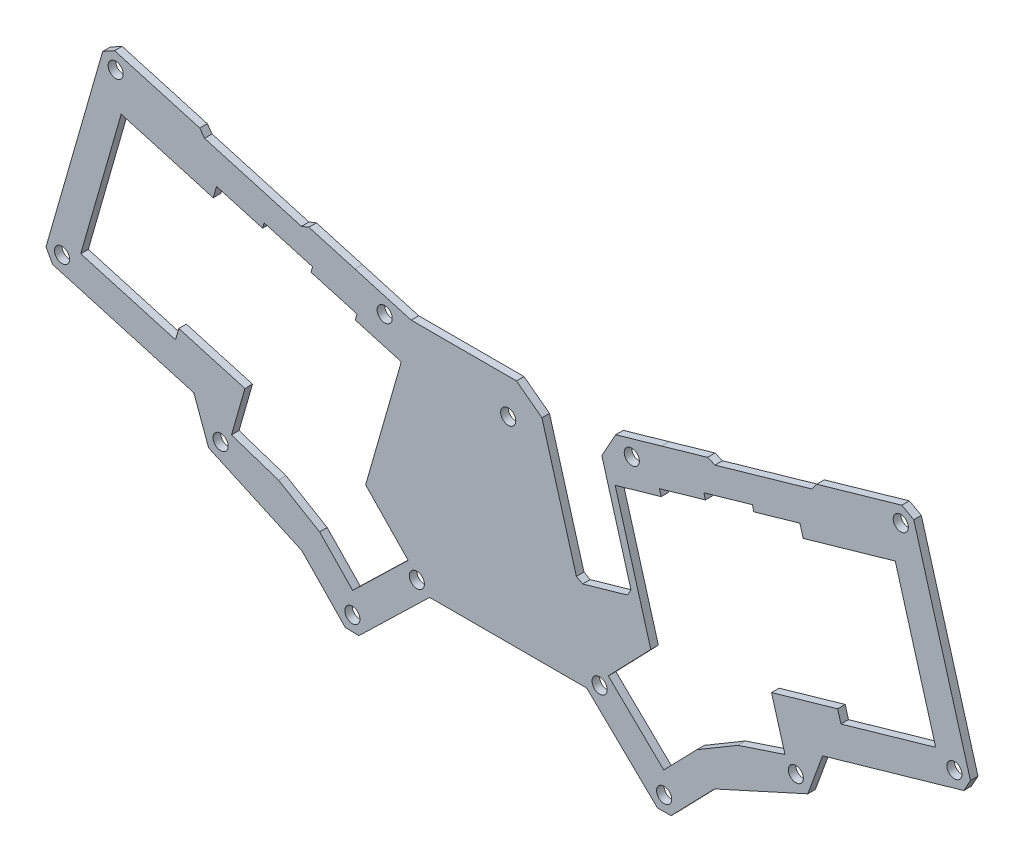
SolidWorks part; units mm, degrees
ref_plane "Plan de face" through (0, 0, 0) normal (0, 0, 1) x (1, 0, 0)
ref_plane "Plan de dessus" through (0, 0, 0) normal (0, 1, 0) x (1, 0, 0)
ref_plane "Plan de droite" through (0, 0, 0) normal (1, 0, 0) x (0, 0, -1)
sketch "Esquisse1" plane through (0, 0, 0) normal (0, 0, 1) x (1, 0, 0)
  line L0 (-121.6461, -32.0475) -> (-108.1875, -28.1884) construction
  line L1 (-108.1875, -28.1884) -> (-104.3283, -41.647) construction
  line L2 (-104.3283, -41.647) -> (-117.7869, -45.5062) construction
  line L3 (-117.7869, -45.5062) -> (-121.6461, -32.0475) construction
  line L4 (-100.1763, -37.9855) -> (-104.0355, -24.5269) construction
  line L5 (-104.0355, -24.5269) -> (-90.5769, -20.6677) construction
  line L6 (-90.5769, -20.6677) -> (-86.7177, -34.1263) construction
  line L7 (-86.7177, -34.1263) -> (-100.1763, -37.9855) construction
  line L8 (-82.5657, -30.4649) -> (-86.4249, -17.0063) construction
  line L9 (-86.4249, -17.0063) -> (-72.9663, -13.1471) construction
  line L10 (-72.9663, -13.1471) -> (-69.1071, -26.6057) construction
  line L11 (-69.1071, -26.6057) -> (-82.5657, -30.4649) construction
  line L12 (-63.6458, -27.5106) -> (-67.505, -14.0519) construction
  line L13 (-67.505, -14.0519) -> (-54.0463, -10.1927) construction
  line L14 (-54.0463, -10.1927) -> (-50.1872, -23.6514) construction
  line L15 (-50.1872, -23.6514) -> (-63.6458, -27.5106) construction
  line L16 (-44.0711, -26.8394) -> (-47.9303, -13.3808) construction
  line L17 (-47.9303, -13.3808) -> (-34.4717, -9.5216) construction
  line L18 (-34.4717, -9.5216) -> (-30.6125, -22.9802) construction
  line L19 (-30.6125, -22.9802) -> (-44.0711, -26.8394) construction
  line L20 (-25.8054, -21.6018) -> (-29.6646, -8.1432) construction
  line L21 (-29.6646, -8.1432) -> (-16.206, -4.284) construction
  line L22 (-16.206, -4.284) -> (-12.3468, -17.7426) construction
  line L23 (-12.3468, -17.7426) -> (-25.8054, -21.6018) construction
  line L24 (-116.4086, -50.3128) -> (-102.95, -46.4536) construction
  line L25 (-102.95, -46.4536) -> (-99.0908, -59.9122) construction
  line L26 (-99.0908, -59.9122) -> (-112.5494, -63.7714) construction
  line L27 (-112.5494, -63.7714) -> (-116.4086, -50.3128) construction
  line L28 (-98.798, -42.7922) -> (-85.3394, -38.933) construction
  line L29 (-85.3394, -38.933) -> (-81.4802, -52.3916) construction
  line L30 (-81.4802, -52.3916) -> (-94.9388, -56.2508) construction
  line L31 (-94.9388, -56.2508) -> (-98.798, -42.7922) construction
  line L32 (-81.1874, -35.2715) -> (-67.7288, -31.4123) construction
  line L33 (-67.7288, -31.4123) -> (-63.8696, -44.8709) construction
  line L34 (-63.8696, -44.8709) -> (-77.3282, -48.7301) construction
  line L35 (-77.3282, -48.7301) -> (-81.1874, -35.2715) construction
  line L36 (-62.2675, -32.3172) -> (-48.8089, -28.458) construction
  line L37 (-48.8089, -28.458) -> (-44.9497, -41.9166) construction
  line L38 (-44.9497, -41.9166) -> (-58.4083, -45.7758) construction
  line L39 (-58.4083, -45.7758) -> (-62.2675, -32.3172) construction
  line L40 (-42.6928, -31.646) -> (-29.2342, -27.7869) construction
  line L41 (-29.2342, -27.7869) -> (-25.375, -41.2455) construction
  line L42 (-25.375, -41.2455) -> (-38.8336, -45.1047) construction
  line L43 (-38.8336, -45.1047) -> (-42.6928, -31.646) construction
  line L44 (-24.4271, -26.4084) -> (-10.9685, -22.5492) construction
  line L45 (-10.9685, -22.5492) -> (-7.1093, -36.0078) construction
  line L46 (-7.1093, -36.0078) -> (-20.5679, -39.867) construction
  line L47 (-20.5679, -39.867) -> (-24.4271, -26.4084) construction
  line L48 (-19.1896, -44.6737) -> (-5.731, -40.8145) construction
  line L49 (-5.731, -40.8145) -> (-1.8718, -54.2731) construction
  line L50 (-1.8718, -54.2731) -> (-15.3304, -58.1323) construction
  line L51 (-15.3304, -58.1323) -> (-19.1896, -44.6737) construction
  line L52 (-37.4554, -49.9113) -> (-23.9967, -46.0521) construction
  line L53 (-23.9967, -46.0521) -> (-20.1376, -59.5107) construction
  line L54 (-20.1376, -59.5107) -> (-33.5962, -63.3699) construction
  line L55 (-33.5962, -63.3699) -> (-37.4554, -49.9113) construction
  line L56 (-57.03, -50.5825) -> (-43.5714, -46.7233) construction
  line L57 (-43.5714, -46.7233) -> (-39.7122, -60.1819) construction
  line L58 (-39.7122, -60.1819) -> (-53.1708, -64.0411) construction
  line L59 (-53.1708, -64.0411) -> (-57.03, -50.5825) construction
  line L60 (-75.9499, -53.5368) -> (-62.4913, -49.6776) construction
  line L61 (-62.4913, -49.6776) -> (-58.6321, -63.1362) construction
  line L62 (-58.6321, -63.1362) -> (-72.0908, -66.9954) construction
  line L63 (-72.0908, -66.9954) -> (-75.9499, -53.5368) construction
  line L64 (-93.5605, -61.0574) -> (-80.1019, -57.1982) construction
  line L65 (-80.1019, -57.1982) -> (-76.2427, -70.6569) construction
  line L66 (-76.2427, -70.6569) -> (-89.7013, -74.516) construction
  line L67 (-89.7013, -74.516) -> (-93.5605, -61.0574) construction
  line L68 (-111.1711, -68.5781) -> (-97.7125, -64.7189) construction
  line L69 (-97.7125, -64.7189) -> (-93.8533, -78.1775) construction
  line L70 (-93.8533, -78.1775) -> (-107.3119, -82.0367) construction
  line L71 (-107.3119, -82.0367) -> (-111.1711, -68.5781) construction
  line L72 (-79.0181, -77.3048) -> (-65.5595, -73.4456) construction
  line L73 (-65.5595, -73.4456) -> (-61.7003, -86.9042) construction
  line L74 (-61.7003, -86.9042) -> (-75.1589, -90.7634) construction
  line L75 (-75.1589, -90.7634) -> (-79.0181, -77.3048) construction
  line L76 (-99.4001, -88.1351) -> (-87.3916, -80.9362)
  line L77 (-87.3916, -80.9362) -> (-80.1927, -92.9448)
  line L78 (-80.1927, -92.9448) -> (-92.2012, -100.1436)
  line L79 (-92.2012, -100.1436) -> (-99.4001, -88.1351)
  line L80 (-120.0498, -100.4367) -> (-110.317, -90.3719)
  line L81 (-110.317, -90.3719) -> (-100.2522, -100.1047)
  line L82 (-100.2522, -100.1047) -> (-109.985, -110.1695)
  line L83 (-109.985, -110.1695) -> (-120.0498, -100.4367)
  line L86 (0.634, -55.7756) -> (-52.9527, -71.1413) construction
  line L89 (-59.2205, -88.2424) -> (-52.9527, -71.1413) construction
  line L96 (-93.4066, -103.0586) -> (-59.4637, -88.3612) construction
  line L97 (-105.418, -115.2057) -> (-93.9754, -103.3509) construction
  line L98 (-126.5332, -96.9919) -> (-107.5003, -115.385) construction
  line L99 (-167.7972, -50.1766) -> (-183.2082, -64.014) construction
  line L100 (-106.3822, -25.4572) -> (-123.6848, -30.4187) construction
  line L101 (-72.1178, -10.6906) -> (-88.4663, -15.3784) construction
  line L102 (-53.2337, -7.6163) -> (-70.5393, -12.5786) construction
  line L103 (-33.6604, -6.9452) -> (-50.9661, -11.9075) construction
  line L104 (-15.3965, -1.7081) -> (-31.745, -6.396) construction
  line L105 (0.5403, -55.2132) -> (-14.6896, -2.0999) construction
  line L106 (-16.199, -60.6113) -> (0.1495, -55.9235) construction
  line L107 (-52.7198, -71.0835) -> (-18.1144, -61.1606) construction
  line L108 (-59.1184, -88.0534) -> (-52.9674, -71.2752) construction
  line L109 (-183.2082, -64.014) -> (-173.1824, -64.9357) construction
  line L113 (-102.2678, -134.438) -> (-84.7238, -116.3191) construction
  line L114 (-84.7238, -116.3191) -> (-47.2969, -99.2981) construction
  line L115 (-47.2969, -99.2981) -> (-41.4917, -83.4594) construction
  line L116 (14.3812, -67.4381) -> (-41.4917, -83.4594) construction
  line L117 (17.8093, -61.2536) -> (-5.1371, 18.7701) construction
  line L122 (-11.3217, 22.1985) -> (-107.4545, -5.3614) construction
  line L129 (-167.7953, -27.6055) -> (-167.7953, -64.7189) construction
  line L130 (-242.0685, -103.8419) -> (-276.37, -88.2424) construction
  line L131 (-229.5108, -116.8112) -> (-242.0685, -103.8419) construction
  line L138 (-208.9328, -96.8551) -> (-229.5108, -116.8112) construction
  line L139 (-225.5107, -79.6567) -> (-208.9328, -96.8551) construction
  line L140 (-109.3352, -134.5492) -> (-102.2678, -134.438) construction
  line L142 (-5.1371, 18.7701) -> (-11.3217, 22.1985) construction
  line L143 (-211.4691, -30.6868) -> (-225.5107, -79.6567) construction
  line L147 (-114.18, -7.2899) -> (-107.4545, -5.3614) construction
  line L148 (-114.18, -7.2899) -> (-123.7936, -10.0465) construction
  line L154 (-118.7579, -16.9241) -> (-12.0005, 13.6817) construction
  line L155 (-131.531, -101.8802) -> (-105.9239, -126.7133) construction
  line L156 (-105.9239, -126.7133) -> (-89.4162, -109.6646) construction
  line L157 (-128.0696, -96.8789) -> (-106.0575, -118.2258)
  line L158 (-106.0575, -118.2258) -> (-92.9354, -104.6737)
  line L161 (1.8709, -56.4612) -> (-35.7408, -67.2462)
  line L162 (1.8709, -56.4612) -> (-14.1861, -0.4639)
  line L163 (-14.1861, -0.4639) -> (-50.7166, -10.9388)
  line L164 (-50.7166, -10.9388) -> (-52.026, -6.3725)
  line L165 (-52.026, -6.3725) -> (-70.2913, -11.61)
  line L166 (-70.2913, -11.61) -> (-70.911, -9.4488)
  line L167 (-70.911, -9.4488) -> (-90.1377, -14.9608)
  line L168 (-90.1377, -14.9608) -> (-89.5177, -17.1231)
  line L169 (-89.5177, -17.1231) -> (-107.783, -22.3606)
  line L170 (-107.783, -22.3606) -> (-107.0938, -24.7639)
  line L171 (-107.0938, -24.7639) -> (-125.3583, -30.0011)
  line L172 (-125.3583, -30.0011) -> (-111.2001, -79.378)
  line L173 (-111.2001, -79.378) -> (-127.3777, -96.1611)
  line L174 (-89.4162, -109.6646) -> (-53.6562, -93.4017) construction
  line L175 (-53.6562, -93.4017) -> (-47.6042, -76.8897) construction
  line L176 (9.2923, -60.5749) -> (-47.6042, -76.8897) construction
  line L177 (9.2923, -60.5749) -> (-12.0005, 13.6817) construction
  line L178 (-229.7336, -25.4495) -> (-211.4691, -30.6868) construction
  line L179 (-229.0444, -23.0462) -> (-229.7336, -25.4495) construction
  line L180 (-173.1824, -64.9357) -> (-167.7972, -60.1004) construction
  line L181 (-247.3097, -17.8087) -> (-229.0444, -23.0462) construction
  line L185 (17.8093, -61.2536) -> (14.3812, -67.4381) construction
  line L186 (-183.2987, -65.7677) -> (-173.2729, -66.6895) construction
  line L187 (-173.2729, -66.6895) -> (-167.8052, -74.7882) construction
  line L190 (-246.6897, -15.6465) -> (-247.3097, -17.8087) construction
  line L191 (-263.9939, -10.6857) -> (-246.6897, -15.6465) construction
  line L192 (-264.6136, -12.8469) -> (-263.9939, -10.6857) construction
  line L193 (-282.8789, -7.6094) -> (-264.6136, -12.8469) construction
  line L194 (-284.1883, -12.1757) -> (-282.8789, -7.6094) construction
  line L195 (-320.7188, -1.7008) -> (-284.1883, -12.1757) construction
  line L196 (-336.2245, -55.7756) -> (-320.7188, -1.7008) construction
  line L197 (-183.2987, -65.7677) -> (-167.8052, -88.0782) construction
  line L198 (-181.8414, -71.5322) -> (-174.8684, -81.0171) construction
  line L199 (-174.8684, -81.0171) -> (-178.3549, -83.9622) construction
  line L200 (-344.8828, -60.5749) -> (-323.5901, 13.6817) construction
  line L201 (-344.8828, -60.5749) -> (-287.9863, -76.8897) construction
  line L202 (-281.9343, -93.4017) -> (-287.9863, -76.8897) construction
  line L203 (-246.1743, -109.6646) -> (-281.9343, -93.4017) construction
  line L204 (-224.3904, -79.378) -> (-208.2128, -96.1611)
  line L205 (-210.2322, -30.0011) -> (-224.3904, -79.378)
  line L206 (-228.4967, -24.7639) -> (-210.2322, -30.0011)
  line L207 (-227.8075, -22.3606) -> (-228.4967, -24.7639)
  line L208 (-246.0728, -17.1231) -> (-227.8075, -22.3606)
  line L209 (-245.4528, -14.9608) -> (-246.0728, -17.1231)
  line L210 (-264.6796, -9.4488) -> (-245.4528, -14.9608)
  line L211 (-265.2993, -11.61) -> (-264.6796, -9.4488)
  line L212 (-283.5645, -6.3725) -> (-265.2993, -11.61)
  line L213 (-284.8739, -10.9388) -> (-283.5645, -6.3725)
  line L217 (0.634, -55.7756) -> (-14.8717, -1.7008) construction
  line L220 (-14.8717, -1.7008) -> (-51.4022, -12.1757) construction
  line L221 (-51.4022, -12.1757) -> (-52.7116, -7.6094) construction
  line L222 (-52.7116, -7.6094) -> (-70.9769, -12.8469) construction
  line L223 (-70.9769, -12.8469) -> (-71.5966, -10.6857) construction
  line L224 (-71.5966, -10.6857) -> (-88.9008, -15.6465) construction
  line L225 (-88.9008, -15.6465) -> (-88.2808, -17.8087) construction
  line L226 (-88.2808, -17.8087) -> (-106.5461, -23.0462) construction
  line L227 (-106.5461, -23.0462) -> (-105.8569, -25.4495) construction
  line L228 (-105.8569, -25.4495) -> (-124.1214, -30.6868) construction
  line L231 (-124.1214, -30.6868) -> (-110.0799, -79.6567) construction
  line L232 (-110.0799, -79.6567) -> (-126.6577, -96.8551) construction
  line L233 (-126.6577, -96.8551) -> (-106.0797, -116.8112) construction
  line L234 (-106.0797, -116.8112) -> (-93.522, -103.8419) construction
  line L235 (-93.522, -103.8419) -> (-59.2205, -88.2424) construction
  line L236 (-321.4044, -0.4639) -> (-284.8739, -10.9388)
  line L237 (-337.4614, -56.4612) -> (-321.4044, -0.4639)
  line L238 (-337.4614, -56.4612) -> (-299.8497, -67.2462)
  line L241 (-229.5331, -118.2258) -> (-242.6551, -104.6737)
  line L242 (-208.2366, -97.573) -> (-229.5331, -118.2258)
  line L243 (-229.6666, -126.7133) -> (-246.1743, -109.6646) construction
  line L244 (-204.0596, -101.8802) -> (-229.6666, -126.7133) construction
  line L245 (-331.2803, 15.8863) -> (-208.2299, -19.3904) construction
  line L246 (-178.3549, -83.9622) -> (-185.8788, -75.0552) construction
  line L247 (-185.8788, -75.0552) -> (-181.8414, -71.5322) construction
  line L248 (-176.7625, -46.6332) -> (-185.5498, -54.5291) construction
  line L249 (-185.5498, -54.5291) -> (-181.1562, -59.4188) construction
  line L250 (-181.1562, -59.4188) -> (-172.3689, -51.5229) construction
  line L251 (-276.4721, -88.0534) -> (-282.6232, -71.2752) construction
  line L252 (-282.8707, -71.0835) -> (-317.4761, -61.1606) construction
  line L253 (-319.3915, -60.6113) -> (-335.74, -55.9235) construction
  line L254 (-336.1309, -55.2132) -> (-320.9009, -2.0999) construction
  line L255 (-320.194, -1.7081) -> (-303.8455, -6.396) construction
  line L256 (-301.9301, -6.9452) -> (-284.6245, -11.9075) construction
  line L257 (-282.3568, -7.6163) -> (-265.0512, -12.5786) construction
  line L258 (-263.4727, -10.6906) -> (-247.1242, -15.3784) construction
  line L259 (-229.2083, -25.4572) -> (-211.9057, -30.4187) construction
  line L260 (-172.3689, -51.5229) -> (-176.7625, -46.6332) construction
  line L261 (-209.0573, -96.9919) -> (-228.0902, -115.385) construction
  line L262 (-230.1725, -115.2057) -> (-241.6151, -103.3509) construction
  line L263 (-242.1839, -103.0586) -> (-276.1268, -88.3612) construction
  line L264 (-276.37, -88.2424) -> (-282.6379, -71.1413) construction
  line L265 (-336.2245, -55.7756) -> (-282.6379, -71.1413) construction
  line L268 (-353.3998, -61.2536) -> (-349.9717, -67.4381) construction
  line L274 (-221.4105, -7.2899) -> (-206.0252, -11.7015) construction
  line L275 (-221.4105, -7.2899) -> (-228.136, -5.3614) construction
  line L276 (-330.4534, 18.7701) -> (-324.2688, 22.1985) construction
  line L277 (-226.2553, -134.5492) -> (-233.3227, -134.438) construction
  line L281 (-324.2688, 22.1985) -> (-228.136, -5.3614) construction
  line L282 (-353.3998, -61.2536) -> (-330.4534, 18.7701) construction
  line L283 (-349.9717, -67.4381) -> (-294.0988, -83.4594) construction
  line L284 (-288.2936, -99.2981) -> (-294.0988, -83.4594) construction
  line L285 (-250.8667, -116.3191) -> (-288.2936, -99.2981) construction
  line L286 (-233.3227, -134.438) -> (-250.8667, -116.3191) construction
  line L288 (-225.6055, -110.1695) -> (-215.5407, -100.4367) construction
  line L289 (-235.3383, -100.1047) -> (-225.6055, -110.1695) construction
  line L290 (-225.2735, -90.3719) -> (-235.3383, -100.1047) construction
  line L291 (-215.5407, -100.4367) -> (-225.2735, -90.3719) construction
  line L292 (-243.3893, -100.1436) -> (-236.1904, -88.1351) construction
  line L293 (-255.3978, -92.9448) -> (-243.3893, -100.1436) construction
  line L294 (-248.1989, -80.9362) -> (-255.3978, -92.9448) construction
  line L295 (-236.1904, -88.1351) -> (-248.1989, -80.9362) construction
  line L296 (-260.4316, -90.7634) -> (-256.5724, -77.3048) construction
  line L297 (-273.8902, -86.9042) -> (-260.4316, -90.7634) construction
  line L298 (-270.031, -73.4456) -> (-273.8902, -86.9042) construction
  line L299 (-256.5724, -77.3048) -> (-270.031, -73.4456) construction
  line L300 (-228.2786, -82.0367) -> (-224.4194, -68.5781) construction
  line L301 (-241.7372, -78.1775) -> (-228.2786, -82.0367) construction
  line L302 (-237.878, -64.7189) -> (-241.7372, -78.1775) construction
  line L303 (-224.4194, -68.5781) -> (-237.878, -64.7189) construction
  line L304 (-245.8892, -74.516) -> (-242.03, -61.0574) construction
  line L305 (-259.3478, -70.6569) -> (-245.8892, -74.516) construction
  line L306 (-255.4886, -57.1982) -> (-259.3478, -70.6569) construction
  line L307 (-242.03, -61.0574) -> (-255.4886, -57.1982) construction
  line L308 (-263.4998, -66.9954) -> (-259.6406, -53.5368) construction
  line L309 (-276.9584, -63.1362) -> (-263.4998, -66.9954) construction
  line L310 (-273.0992, -49.6776) -> (-276.9584, -63.1362) construction
  line L311 (-259.6406, -53.5368) -> (-273.0992, -49.6776) construction
  line L312 (-282.4197, -64.0411) -> (-278.5605, -50.5825) construction
  line L313 (-295.8783, -60.1819) -> (-282.4197, -64.0411) construction
  line L314 (-292.0191, -46.7233) -> (-295.8783, -60.1819) construction
  line L315 (-278.5605, -50.5825) -> (-292.0191, -46.7233) construction
  line L316 (-301.9944, -63.3699) -> (-298.1352, -49.9113) construction
  line L317 (-315.453, -59.5107) -> (-301.9944, -63.3699) construction
  line L318 (-311.5938, -46.0521) -> (-315.453, -59.5107) construction
  line L319 (-298.1352, -49.9113) -> (-311.5938, -46.0521) construction
  line L320 (-320.2601, -58.1323) -> (-316.4009, -44.6737) construction
  line L321 (-333.7187, -54.2731) -> (-320.2601, -58.1323) construction
  line L322 (-329.8595, -40.8145) -> (-333.7187, -54.2731) construction
  line L323 (-316.4009, -44.6737) -> (-329.8595, -40.8145) construction
  line L324 (-315.0226, -39.867) -> (-311.1634, -26.4084) construction
  line L325 (-328.4812, -36.0078) -> (-315.0226, -39.867) construction
  line L326 (-324.622, -22.5492) -> (-328.4812, -36.0078) construction
  line L327 (-311.1634, -26.4084) -> (-324.622, -22.5492) construction
  line L328 (-296.7569, -45.1047) -> (-292.8977, -31.646) construction
  line L329 (-310.2155, -41.2455) -> (-296.7569, -45.1047) construction
  line L330 (-306.3563, -27.7869) -> (-310.2155, -41.2455) construction
  line L331 (-292.8977, -31.646) -> (-306.3563, -27.7869) construction
  line L332 (-277.1822, -45.7758) -> (-273.323, -32.3172) construction
  line L333 (-290.6408, -41.9166) -> (-277.1822, -45.7758) construction
  line L334 (-286.7817, -28.458) -> (-290.6408, -41.9166) construction
  line L335 (-273.323, -32.3172) -> (-286.7817, -28.458) construction
  line L336 (-258.2623, -48.7301) -> (-254.4031, -35.2715) construction
  line L337 (-271.7209, -44.8709) -> (-258.2623, -48.7301) construction
  line L338 (-267.8617, -31.4123) -> (-271.7209, -44.8709) construction
  line L339 (-254.4031, -35.2715) -> (-267.8617, -31.4123) construction
  line L340 (-240.6517, -56.2508) -> (-236.7925, -42.7922) construction
  line L341 (-254.1103, -52.3916) -> (-240.6517, -56.2508) construction
  line L342 (-250.2511, -38.933) -> (-254.1103, -52.3916) construction
  line L343 (-236.7925, -42.7922) -> (-250.2511, -38.933) construction
  line L344 (-223.0411, -63.7714) -> (-219.1819, -50.3128) construction
  line L345 (-236.4997, -59.9122) -> (-223.0411, -63.7714) construction
  line L346 (-232.6405, -46.4536) -> (-236.4997, -59.9122) construction
  line L347 (-219.1819, -50.3128) -> (-232.6405, -46.4536) construction
  line L348 (-323.2438, -17.7426) -> (-309.7851, -21.6018) construction
  line L349 (-319.3846, -4.284) -> (-323.2438, -17.7426) construction
  line L350 (-305.926, -8.1432) -> (-319.3846, -4.284) construction
  line L351 (-309.7851, -21.6018) -> (-305.926, -8.1432) construction
  line L352 (-304.978, -22.9802) -> (-291.5194, -26.8394) construction
  line L353 (-301.1188, -9.5216) -> (-304.978, -22.9802) construction
  line L354 (-287.6602, -13.3808) -> (-301.1188, -9.5216) construction
  line L355 (-291.5194, -26.8394) -> (-287.6602, -13.3808) construction
  line L356 (-285.4034, -23.6514) -> (-271.9448, -27.5106) construction
  line L357 (-281.5442, -10.1927) -> (-285.4034, -23.6514) construction
  line L358 (-268.0856, -14.0519) -> (-281.5442, -10.1927) construction
  line L359 (-271.9448, -27.5106) -> (-268.0856, -14.0519) construction
  line L360 (-266.4834, -26.6057) -> (-253.0248, -30.4649) construction
  line L361 (-262.6242, -13.1471) -> (-266.4834, -26.6057) construction
  line L362 (-249.1656, -17.0063) -> (-262.6242, -13.1471) construction
  line L363 (-253.0248, -30.4649) -> (-249.1656, -17.0063) construction
  line L364 (-248.8728, -34.1263) -> (-235.4142, -37.9855) construction
  line L365 (-245.0136, -20.6677) -> (-248.8728, -34.1263) construction
  line L366 (-231.555, -24.5269) -> (-245.0136, -20.6677) construction
  line L367 (-235.4142, -37.9855) -> (-231.555, -24.5269) construction
  line L368 (-217.8036, -45.5062) -> (-213.9444, -32.0475) construction
  line L369 (-231.2622, -41.647) -> (-217.8036, -45.5062) construction
  line L370 (-227.4031, -28.1884) -> (-231.2622, -41.647) construction
  line L371 (-213.9444, -32.0475) -> (-227.4031, -28.1884) construction
  line L372 (-226.2553, -134.5492) -> (-194.0347, -103.3509) construction
  line L373 (-109.3352, -134.5492) -> (-141.5559, -103.3509) construction
  line L374 (-141.5559, -103.3509) -> (-194.0347, -103.3509) construction
  line L375 (-167.7972, -50.1766) -> (-152.3861, -64.014) construction
  line L376 (-162.4119, -64.9357) -> (-167.7972, -60.1004) construction
  line L377 (-162.3376, -66.6895) -> (-167.8052, -74.7882) construction
  line L378 (-152.3118, -65.7677) -> (-167.8052, -88.0782) construction
  line L379 (-163.2254, -51.5229) -> (-158.8318, -46.6332) construction
  line L380 (-154.4381, -59.4188) -> (-163.2254, -51.5229) construction
  line L381 (-150.0445, -54.5291) -> (-154.4381, -59.4188) construction
  line L382 (-158.8318, -46.6332) -> (-150.0445, -54.5291) construction
  line L383 (-149.7316, -75.0552) -> (-153.7691, -71.5322) construction
  line L384 (-157.2555, -83.9622) -> (-149.7316, -75.0552) construction
  line L385 (-160.742, -81.0171) -> (-157.2555, -83.9622) construction
  line L386 (-153.7691, -71.5322) -> (-160.742, -81.0171) construction
  line L387 (-152.3118, -65.7677) -> (-162.3376, -66.6895) construction
  line L388 (-152.3861, -64.014) -> (-162.4119, -64.9357) construction
  line L389 (-206.0252, -11.7015) -> (-129.5654, -11.7015) construction
  line L390 (-119.0708, -62.7964) -> (-130.6498, -22.4155)
  line L391 (-123.5545, -47.16) -> (-127.4136, -33.7014) construction
  line L392 (-120.442, -65.2702) -> (-138.2688, -70.3819)
  line L393 (-140.7426, -69.0107) -> (-154.4194, -21.3141)
  line L394 (-167.1758, -11.7015) -> (-206.0252, -11.7015) construction
  line L395 (-154.4194, -21.3141) -> (-167.1758, -11.7015) construction
  line L396 (-123.7936, -10.0465) -> (-130.6498, -22.4155) construction
  line L397 (-138.2688, -70.3819) -> (-140.7426, -69.0107)
  line L398 (-119.0708, -62.7964) -> (-120.442, -65.2702)
  line L399 (-129.5654, -11.7015) -> (-123.7936, -10.0465) construction
  line L400 (-165.8487, -12.7015) -> (-206.1657, -12.7015) construction
  line L401 (-221.6861, -8.2511) -> (-206.1657, -12.7015) construction
  line L402 (-221.6861, -8.2511) -> (-228.4116, -6.3226) construction
  line L403 (-324.1462, 21.1231) -> (-228.4116, -6.3226) construction
  line L404 (-329.6063, 18.0963) -> (-324.1462, 21.1231) construction
  line L405 (-352.3244, -61.1311) -> (-329.6063, 18.0963) construction
  line L406 (-352.3244, -61.1311) -> (-349.2979, -66.591) construction
  line L407 (-349.2979, -66.591) -> (-293.3347, -82.6382) construction
  line L408 (-287.4987, -98.561) -> (-293.3347, -82.6382) construction
  line L409 (-250.2802, -115.4872) -> (-287.4987, -98.561) construction
  line L410 (-232.8926, -133.4446) -> (-250.2802, -115.4872) construction
  line L411 (-226.6535, -133.5428) -> (-232.8926, -133.4446) construction
  line L412 (-226.6535, -133.5428) -> (-194.4395, -102.3509) construction
  line L413 (-141.1511, -102.3509) -> (-194.4395, -102.3509) construction
  line L414 (-108.937, -133.5428) -> (-141.1511, -102.3509) construction
  line L415 (-108.937, -133.5428) -> (-102.6979, -133.4446) construction
  line L416 (-102.6979, -133.4446) -> (-85.3104, -115.4872) construction
  line L417 (-85.3104, -115.4872) -> (-48.0918, -98.561) construction
  line L418 (-48.0918, -98.561) -> (-42.2558, -82.6382) construction
  line L419 (13.7074, -66.591) -> (-42.2558, -82.6382) construction
  line L420 (16.7339, -61.1311) -> (13.7074, -66.591) construction
  line L421 (16.7339, -61.1311) -> (-5.9842, 18.0963) construction
  line L422 (-5.9842, 18.0963) -> (-11.4443, 21.1231) construction
  line L423 (-11.4443, 21.1231) -> (-107.1789, -6.3226) construction
  line L424 (-113.9044, -8.2511) -> (-107.1789, -6.3226) construction
  line L425 (-113.9044, -8.2511) -> (-124.4792, -11.2834) construction
  line L426 (-167.1758, -12.7015) -> (-206.1657, -12.7015) construction
  line L427 (-113.9044, -8.2511) -> (-123.5179, -11.0078) construction
  line L428 (-165.8487, -12.7015) -> (-154.4194, -21.3141) construction
  line L429 (-130.6498, -22.4155) -> (-124.4792, -11.2834) construction
  line L430 (-208.2366, -97.573) -> (-207.4919, -96.8551)
  line L431 (-207.4919, -96.8551) -> (-208.2128, -96.1611)
  line L432 (-127.3777, -96.1611) -> (-128.0696, -96.8789)
  line L433 (-221.9618, -9.2124) -> (-206.3062, -13.7015)
  line L434 (-164.5217, -13.7015) -> (-206.3062, -13.7015)
  line L435 (-166.1833, -13.7015) -> (-155.2884, -21.9114) construction
  line L436 (-141.5897, -69.6845) -> (-155.2884, -21.9114) construction
  line L437 (-138.3914, -71.4574) -> (-141.5897, -69.6845) construction
  line L438 (-119.7682, -66.1172) -> (-138.3914, -71.4574) construction
  line L439 (-117.9954, -62.9189) -> (-119.7682, -66.1172) construction
  line L440 (-117.9954, -62.9189) -> (-129.5744, -22.538) construction
  line L441 (-129.5744, -22.538) -> (-123.8054, -12.1305) construction
  line L442 (-113.6287, -9.2124) -> (-125.1648, -12.5203)
  line L443 (-113.6287, -9.2124) -> (-106.9033, -7.2839)
  line L444 (-11.5669, 20.0477) -> (-45.3689, 10.3571)
  line L445 (-6.8313, 17.4225) -> (-11.5669, 20.0477)
  line L446 (15.6584, -61.0086) -> (-6.8313, 17.4225)
  line L447 (15.6584, -61.0086) -> (13.0336, -65.7439)
  line L448 (13.0336, -65.7439) -> (-43.0198, -81.817)
  line L449 (-48.8867, -97.824) -> (-43.0198, -81.817)
  line L450 (-85.8969, -114.6554) -> (-48.8867, -97.824)
  line L451 (-103.128, -132.4513) -> (-85.8969, -114.6554)
  line L452 (-108.5388, -132.5364) -> (-103.128, -132.4513)
  line L453 (-108.5388, -132.5364) -> (-136.6152, -105.3509)
  line L454 (-140.7463, -101.3509) -> (-194.8443, -101.3509) construction
  line L455 (-227.0517, -132.5364) -> (-198.9754, -105.3509)
  line L456 (-227.0517, -132.5364) -> (-232.4625, -132.4513)
  line L457 (-232.4625, -132.4513) -> (-249.6936, -114.6554)
  line L458 (-249.6936, -114.6554) -> (-286.7038, -97.824)
  line L459 (-286.7038, -97.824) -> (-292.5707, -81.817)
  line L460 (-348.6241, -65.7439) -> (-292.5707, -81.817)
  line L461 (-351.2489, -61.0086) -> (-348.6241, -65.7439)
  line L462 (-351.2489, -61.0086) -> (-328.7592, 17.4225)
  line L463 (-328.7592, 17.4225) -> (-324.0237, 20.0477)
  line L464 (-324.0237, 20.0477) -> (-228.6872, -7.2839)
  line L465 (-221.9618, -9.2124) -> (-228.6872, -7.2839)
  line L466 (-166.1833, -13.7015) -> (-206.3062, -13.7015) construction
  line L467 (-113.6287, -9.2124) -> (-123.8054, -12.1305) construction
  line L468 (-130.6498, -22.4155) -> (-125.1648, -12.5203)
  line L469 (-154.4194, -21.3141) -> (-164.5217, -13.7015)
  line L470 (-132.4841, -109.3509) -> (-203.1064, -109.3509) construction
  line L471 (-140.7463, -109.3509) -> (-194.8443, -109.3509) construction
  line L472 (-92.9354, -104.6737) -> (-76.6212, -95.0127)
  line L473 (-227.0517, -132.5364) -> (-194.8443, -101.3509) construction
  line L474 (-108.5388, -132.5364) -> (-140.7463, -101.3509) construction
  line L475 (-76.6212, -95.0127) -> (-57.9612, -88.8254)
  line L476 (-57.9612, -88.8254) -> (-63.3014, -70.2021)
  line L477 (-37.0515, -62.6751) -> (-63.3014, -70.2021)
  line L478 (-37.0515, -62.6751) -> (-35.7408, -67.2462)
  line L479 (-242.6551, -104.6737) -> (-258.9693, -95.0127)
  line L480 (-258.9693, -95.0127) -> (-277.6293, -88.8254)
  line L481 (-277.6293, -88.8254) -> (-272.2891, -70.2021)
  line L482 (-298.539, -62.6751) -> (-272.2891, -70.2021)
  line L483 (-298.539, -62.6751) -> (-299.8497, -67.2462)
  line L484 (-66.4927, 2.2629) -> (-65.3792, -1.6212) construction
  line L485 (-85.7183, -3.2488) -> (-47.2672, 7.7746)
  line L486 (-88.6965, -2.0643) -> (-85.7183, -3.2488)
  line L487 (-45.3689, 10.3571) -> (-47.2672, 7.7746)
  line L488 (-88.6965, -2.0643) -> (-106.9033, -7.2839)
  line L489 (-246.894, -2.0643) -> (-249.8723, -3.2488)
  line L490 (-11.5669, 20.0477) -> (-106.9033, -7.2839) construction
  line L491 (-249.8723, -3.2488) -> (-288.3233, 7.7746)
  line L492 (-290.2216, 10.3571) -> (-288.3233, 7.7746)
  line L493 (-134.5496, -107.3509) -> (-201.0409, -107.3509) construction
  line L494 (-136.6152, -105.3509) -> (-198.9754, -105.3509)
  line L495 (-132.4841, -107.3509) -> (-203.1064, -107.3509) construction
  line L497 (-134.5496, -105.3509) -> (-201.0409, -105.3509) construction
  circle A2 centre (-12.0005, 13.6817) radius 1.6 construction
  circle A3 centre (-12.0005, 13.6817) radius 3
  circle A4 centre (-118.7579, -16.9241) radius 3
  circle A5 centre (9.2923, -60.5749) radius 3
  circle A6 centre (-53.6562, -93.4017) radius 3
  circle A7 centre (-105.9239, -126.7133) radius 3
  circle A8 centre (-131.531, -101.8802) radius 3
  circle A10 centre (-147.4897, -45.973) radius 1.6 construction
  circle A11 centre (-323.5901, 13.6817) radius 3
  circle A12 centre (-188.1008, -45.973) radius 1.6 construction
  circle A14 centre (-204.0596, -101.8802) radius 3
  circle A15 centre (-229.6666, -126.7133) radius 3
  circle A16 centre (-281.9343, -93.4017) radius 3
  circle A17 centre (-344.8828, -60.5749) radius 3
  circle A18 centre (-216.8326, -16.9241) radius 3
  circle A19 centre (-323.5901, 13.6817) radius 1.6 construction
  circle A20 centre (-167.7953, -27.6055) radius 3
  point P138 (-167.7953, -27.6055)
  point P139 (-6.5153, 23.5764)
  point P150 (-169.1046, -23.0392)
  point P200 (19.1875, -66.0599)
  point P203 (-141.5228, -71.3355)
  point P204 (-141.5228, 1.5705)
  point P263 (-133.4062, -12.8029)
  point P264 (-118.5195, -64.7189)
  point P283 (-140.1914, -70.9332)
  point P284 (-157.1758, -11.7015)
  point P405 (-354.778, -66.0599)
  point P406 (-329.0752, 23.5764)
  point P484 (-65.3792, -1.6212)
  dimension "D3" = 3.2
  dimension "D4" = 6
  dimension "D6" = 6
  dimension "D7" = 6
  dimension "D8" = 6
  dimension "D9" = 6
  dimension "D10" = 6
  dimension "D16" = 3.2
  dimension "D14" = 6
  dimension "D2" = 6
  dimension "D5" = 1
  dimension "D11" = 1
  dimension "D18" = 8
  dimension "D20" = 2
  dimension "D21" = 2
extrude "Boss.-Extru.1" add sketch "Esquisse1" along normal blind 3 contours L433 L465 L464 L463 L462 L461 L460 L459 L458 L457 L456 L455 L454 L453 L452 L451 L450 L449 L448 L447 L446 L445 L444 L443 L442 L441 L440 L439 L438 L437 L436 L435 L434 A18 A16 A14 L432 L173 L172 L171 L170 L169 L168 L167 L166 L165 L164 region at (-170.1626, -54.7515, 0)
sketch "Esquisse2" plane through (0, 0, 3) normal (0, 0, 1) x (1, 0, 0)
  line L0 (-167.7953, -109.3509) -> (-167.7953, -102.3509) construction
  line L1 (-132.4841, -109.3509) -> (-203.1064, -109.3509) construction
  line L2 (-168.7953, -109.3509) -> (-168.7953, -102.3509)
  line L3 (-166.7953, -109.3509) -> (-166.7953, -102.3509)
  line L4 (-163.7953, -109.3509) -> (-163.7953, -102.3509) construction
  line L5 (-164.7953, -109.3509) -> (-164.7953, -102.3509)
  line L6 (-162.7953, -109.3509) -> (-162.7953, -102.3509)
  line L7 (-159.7953, -109.3509) -> (-159.7953, -102.3509) construction
  line L8 (-160.7953, -109.3509) -> (-160.7953, -102.3509)
  line L9 (-158.7953, -109.3509) -> (-158.7953, -102.3509)
  line L10 (-155.7953, -109.3509) -> (-155.7953, -102.3509) construction
  line L11 (-156.7953, -109.3509) -> (-156.7953, -102.3509)
  line L12 (-154.7953, -109.3509) -> (-154.7953, -102.3509)
  line L13 (-151.7953, -109.3509) -> (-151.7953, -102.3509) construction
  line L14 (-152.7953, -109.3509) -> (-152.7953, -102.3509)
  line L15 (-150.7953, -109.3509) -> (-150.7953, -102.3509)
  line L16 (-147.7953, -109.3509) -> (-147.7953, -102.3509) construction
  line L17 (-148.7953, -109.3509) -> (-148.7953, -102.3509)
  line L18 (-146.7953, -109.3509) -> (-146.7953, -102.3509)
  line L19 (-171.7953, -109.3509) -> (-171.7953, -102.3509) construction
  line L20 (-172.7953, -109.3509) -> (-172.7953, -102.3509)
  line L21 (-170.7953, -109.3509) -> (-170.7953, -102.3509)
  line L22 (-175.7953, -109.3509) -> (-175.7953, -102.3509) construction
  line L23 (-176.7953, -109.3509) -> (-176.7953, -102.3509)
  line L24 (-174.7953, -109.3509) -> (-174.7953, -102.3509)
  line L25 (-179.7953, -109.3509) -> (-179.7953, -102.3509) construction
  line L26 (-180.7953, -109.3509) -> (-180.7953, -102.3509)
  line L27 (-178.7953, -109.3509) -> (-178.7953, -102.3509)
  line L28 (-183.7953, -109.3509) -> (-183.7953, -102.3509) construction
  line L29 (-184.7953, -109.3509) -> (-184.7953, -102.3509)
  line L30 (-182.7953, -109.3509) -> (-182.7953, -102.3509)
  line L31 (-187.7953, -109.3509) -> (-187.7953, -102.3509) construction
  line L32 (-188.7953, -109.3509) -> (-188.7953, -102.3509)
  line L33 (-186.7953, -109.3509) -> (-186.7953, -102.3509)
  arc A0 (-168.7953, -109.3509) -> (-166.7953, -109.3509) centre (-167.7953, -109.3509) ccw
  arc A1 (-166.7953, -102.3509) -> (-168.7953, -102.3509) centre (-167.7953, -102.3509) ccw
  arc A2 (-164.7953, -109.3509) -> (-162.7953, -109.3509) centre (-163.7953, -109.3509) ccw
  arc A3 (-162.7953, -102.3509) -> (-164.7953, -102.3509) centre (-163.7953, -102.3509) ccw
  arc A4 (-160.7953, -109.3509) -> (-158.7953, -109.3509) centre (-159.7953, -109.3509) ccw
  arc A5 (-158.7953, -102.3509) -> (-160.7953, -102.3509) centre (-159.7953, -102.3509) ccw
  arc A6 (-156.7953, -109.3509) -> (-154.7953, -109.3509) centre (-155.7953, -109.3509) ccw
  arc A7 (-154.7953, -102.3509) -> (-156.7953, -102.3509) centre (-155.7953, -102.3509) ccw
  arc A8 (-152.7953, -109.3509) -> (-150.7953, -109.3509) centre (-151.7953, -109.3509) ccw
  arc A9 (-150.7953, -102.3509) -> (-152.7953, -102.3509) centre (-151.7953, -102.3509) ccw
  arc A10 (-148.7953, -109.3509) -> (-146.7953, -109.3509) centre (-147.7953, -109.3509) ccw
  arc A11 (-146.7953, -102.3509) -> (-148.7953, -102.3509) centre (-147.7953, -102.3509) ccw
  arc A12 (-172.7953, -109.3509) -> (-170.7953, -109.3509) centre (-171.7953, -109.3509) ccw
  arc A13 (-170.7953, -102.3509) -> (-172.7953, -102.3509) centre (-171.7953, -102.3509) ccw
  arc A14 (-176.7953, -109.3509) -> (-174.7953, -109.3509) centre (-175.7953, -109.3509) ccw
  arc A15 (-174.7953, -102.3509) -> (-176.7953, -102.3509) centre (-175.7953, -102.3509) ccw
  arc A16 (-180.7953, -109.3509) -> (-178.7953, -109.3509) centre (-179.7953, -109.3509) ccw
  arc A17 (-178.7953, -102.3509) -> (-180.7953, -102.3509) centre (-179.7953, -102.3509) ccw
  arc A18 (-184.7953, -109.3509) -> (-182.7953, -109.3509) centre (-183.7953, -109.3509) ccw
  arc A19 (-182.7953, -102.3509) -> (-184.7953, -102.3509) centre (-183.7953, -102.3509) ccw
  arc A20 (-188.7953, -109.3509) -> (-186.7953, -109.3509) centre (-187.7953, -109.3509) ccw
  arc A21 (-186.7953, -102.3509) -> (-188.7953, -102.3509) centre (-187.7953, -102.3509) ccw
  point P4 (-167.7953, -105.8509)
  point P12 (-163.7953, -105.8509)
  point P19 (-159.7953, -105.8509)
  point P26 (-155.7953, -105.8509)
  point P33 (-151.7953, -105.8509)
  point P40 (-147.7953, -105.8509)
  point P47 (-171.7953, -105.8509)
  point P54 (-175.7953, -105.8509)
  point P61 (-179.7953, -105.8509)
  point P68 (-183.7953, -105.8509)
  point P75 (-187.7953, -105.8509)
  dimension "D1" = 6
  dimension "D2" = 6
